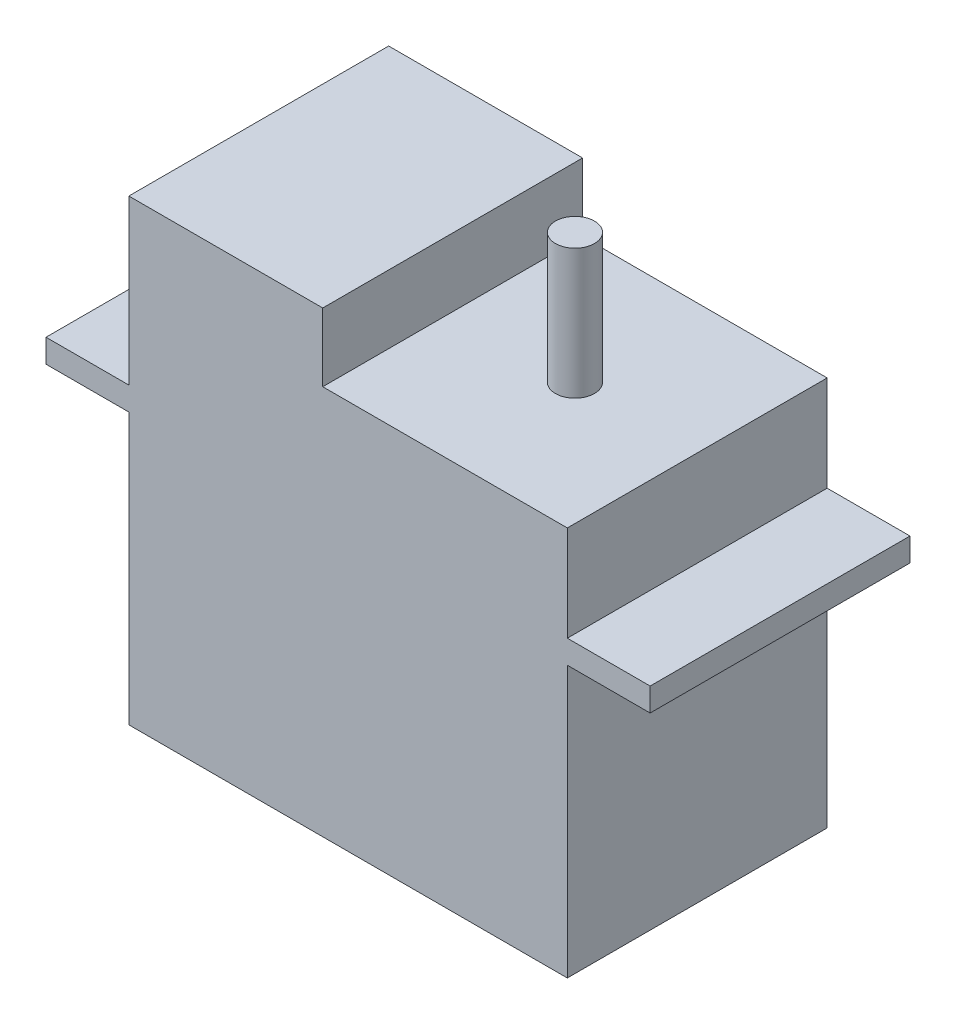
SolidWorks part; units mm, degrees
ref_plane "Plan de face" through (0, 0, 0) normal (0, 0, 1) x (1, 0, 0)
ref_plane "Plan de dessus" through (0, 0, 0) normal (0, 1, 0) x (1, 0, 0)
ref_plane "Plan de droite" through (0, 0, 0) normal (1, 0, 0) x (0, 0, -1)
sketch "Esquisse1" plane through (0, 0, 0) normal (0, 0, 1) x (1, 0, 0)
  line L0 (0, 0) -> (33.75, 0)
  line L1 (33.75, 0) -> (33.75, 22.65) construction
  line L2 (33.75, 22.65) -> (40.125, 22.65)
  line L3 (40.125, 22.65) -> (40.125, 20.85)
  line L4 (40.125, 20.85) -> (33.75, 20.85)
  line L5 (33.75, 20.85) -> (33.75, 30) construction
  line L6 (33.75, 30) -> (14.925, 30)
  line L7 (14.925, 30) -> (14.925, 35.25)
  line L8 (14.925, 35.25) -> (0, 35.25)
  line L9 (0, 35.25) -> (0, 20.85) construction
  line L10 (0, 20.85) -> (-6.375, 20.85)
  line L11 (-6.375, 20.85) -> (-6.375, 22.65)
  line L12 (-6.375, 22.65) -> (0, 22.65)
  line L13 (0, 22.65) -> (0, 0) construction
  line L14 (0, 35.25) -> (0, 22.65)
  line L15 (0, 20.85) -> (0, 0)
  line L16 (33.75, 20.85) -> (33.75, 0)
  line L17 (33.75, 30) -> (33.75, 22.65)
  dimension "D1" = 46.5
  dimension "D2" = 22.65
  dimension "D3" = 35.25
  dimension "D4" = 30
  dimension "D5" = 1.8
  dimension "D6" = 33.75
  dimension "D7" = 25.2
extrude "Boss.-Extru.1" add sketch "Esquisse1" along normal blind 10 and the other way blind 10 contours L6 L7 L8 L14 L12 L11 L10 L15 L0 L16 L4 L3 L2 L17
sketch "Esquisse3" plane through (0, 30, 0) normal (0, 1, 0) x (1, 0, 0)
  line L1 (0, 0) -> (24.3375, 0) construction
  line L3 (24.3375, 0) -> (33.75, -10) construction
  line L4 (33.75, -10) -> (33.75, 10) construction
  line L5 (33.75, 10) -> (24.3375, 0) construction
  line L6 (24.3375, 0) -> (14.925, 10) construction
  line L7 (14.925, 10) -> (14.925, -10) construction
  line L8 (14.925, -10) -> (24.3375, 0) construction
  circle A0 centre (24.3375, 0) radius 1.5
  dimension "D1" = 3
extrude "Boss.-Extru.2" add sketch "Esquisse3" along normal blind 10
ref_plane "Plan1" through (0, 0, 0) normal (0, 0, 1) x (1, 0, 0)
ref_plane "Plan2" through (24.3375, 0, 0) normal (1, 0, 0) x (0, 0, -1)
